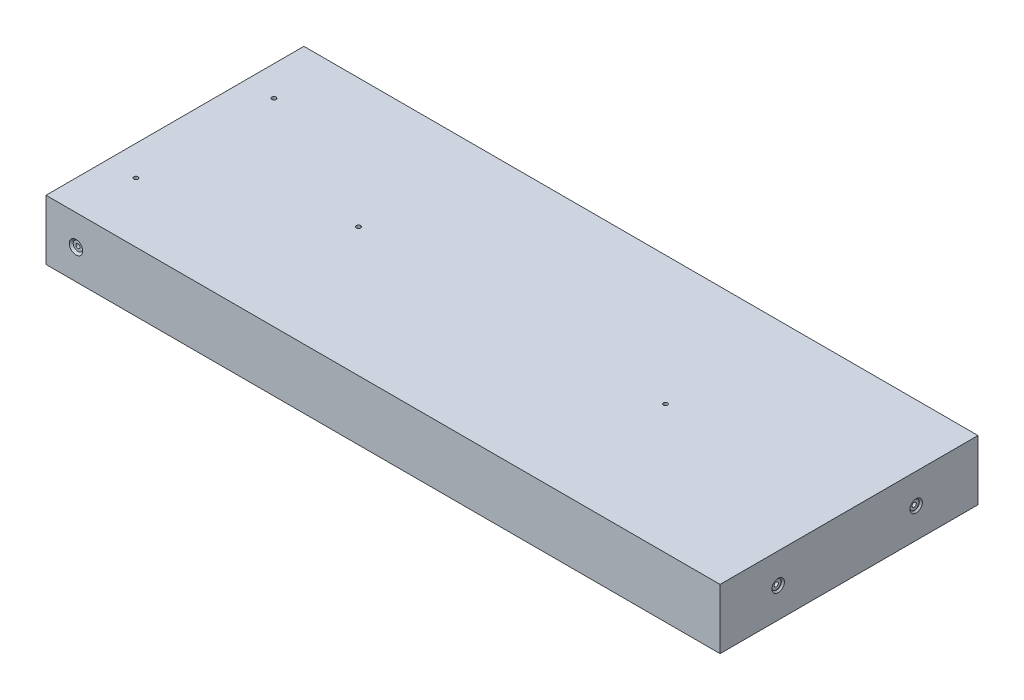
SolidWorks part; units mm, degrees
ref_plane "Front Plane" through (0, 0, 0) normal (0, 0, 1) x (1, 0, 0)
ref_plane "Top Plane" through (0, 0, 0) normal (0, 1, 0) x (1, 0, 0)
ref_plane "Right Plane" through (0, 0, 0) normal (1, 0, 0) x (0, 0, -1)
sketch "Sketch1" plane through (0, 0, 0) normal (0, 1, 0) x (1, 0, 0)
  line L1 (-142.7, 54.6) -> (142.7, 54.6)
  line L2 (-142.7, 54.6) -> (-142.7, -54.6)
  line L3 (-142.7, -54.6) -> (142.7, -54.6)
  line L4 (142.7, 54.6) -> (142.7, -54.6)
  line L5 (-142.7, 54.6) -> (142.7, -54.6) construction
  line L6 (-142.7, -54.6) -> (142.7, 54.6) construction
  point P0 (0, 0)
  dimension "D1" = 109.2
  dimension "D2" = 285.4
extrude "Boss-Extrude1" add sketch "Sketch1" along normal blind 25.4
hole_wizard "CBORE for #0 Binding Head Machine Screw1" positions "Sketch2" profile "Sketch3" counterbore size "#0" standard "ANSI Inch"
sketch "Sketch2" plane through (0, 0, 54.6) normal (0, 0, 1) x (1, 0, 0)
  line L0 (-142.7, 25.4) -> (-142.7, 0) construction
  line L1 (-142.7, 25.4) -> (142.7, 25.4) construction
  point P0 (-130, 12.7)
  dimension "D1" = 12.7
  dimension "D2" = 12.7
sketch "Sketch3" plane through (-130, 12.7, 54.6) normal (1, 0, 0) x (0, -1, 0)
  line L0 (0, 0) -> (0, 30.5342)
  line L1 (0, 30.5342) -> (0.889, 30)
  line L2 (0.889, 30) -> (0.889, 0.8128)
  line L3 (0.889, 0.8128) -> (1.985, 0.8128)
  line L5 (1.985, 0.8128) -> (1.985, 0.8725)
  line L6 (1.985, 0.8725) -> (2.8575, 0)
  line L7 (2.8575, 0) -> (0, 0)
  line L8 (-1.985, 0.8725) -> (-2.8575, 0) construction
  line L10 (0, 30.5342) -> (-0.889, 30) construction
  line L11 (0, -6.35) -> (0, 107.95) construction
  dimension "Hole Dia." = 1.778
  dimension "Hole Depth" = 30
  dimension "C'Bore Dia." = 3.97
  dimension "C'Bore Depth" = 0.8128
  dimension "Near C'Sink Dia." = 5.715
  dimension "Near C'Sink Angle" = 90
  dimension "Drill Angle" = 118
mirror "Mirror1" about plane through (0, 0, 0) normal (0, 0, 1) of "CBORE for #0 Binding Head Machine Screw1"
hole_wizard "CBORE for #0 Binding Head Machine Screw2" positions "Sketch4" profile "Sketch5" counterbore size "#0" standard "ANSI Inch"
sketch "Sketch4" plane through (142.7, 0, 0) normal (1, 0, 0) x (0, 0, -1)
  line L0 (-54.6, 25.4) -> (-54.6, 0) construction
  line L2 (-54.6, 25.4) -> (54.6, 25.4) construction
  point P0 (-30, 12.7)
  point P2 (28.4, 12.7)
  dimension "D1" = 58.4
  dimension "D2" = 24.6
  dimension "D4" = 12.7
sketch "Sketch5" plane through (142.7, 12.7, 30) normal (0, 1, 0) x (0, 0, -1)
  line L0 (0, 0) -> (0, 30.5342)
  line L1 (0, 30.5342) -> (0.889, 30)
  line L2 (0.889, 30) -> (0.889, 0.8128)
  line L3 (0.889, 0.8128) -> (1.985, 0.8128)
  line L5 (1.985, 0.8128) -> (1.985, 0.635)
  line L6 (1.985, 0.635) -> (2.62, 0)
  line L7 (2.62, 0) -> (0, 0)
  line L8 (-1.985, 0.635) -> (-2.62, 0) construction
  line L10 (0, 30.5342) -> (-0.889, 30) construction
  line L11 (0, -6.35) -> (0, 107.95) construction
  dimension "Hole Dia." = 1.778
  dimension "Hole Depth" = 30
  dimension "C'Bore Dia." = 3.97
  dimension "C'Bore Depth" = 0.8128
  dimension "Near C'Sink Dia." = 5.24
  dimension "Near C'Sink Angle" = 90
  dimension "Drill Angle" = 118
hole_wizard "CBORE for #0 Binding Head Machine Screw4" positions "Sketch8" profile "Sketch9" counterbore size "#0" standard "ANSI Inch"
sketch "Sketch8" plane through (0, 0, 0) normal (0, -1, 0) x (-1, 0, 0)
  line L0 (0, 54.6) -> (0, -54.6) construction
  line L1 (-142.7, 54.6) -> (142.7, 54.6) construction
  line L2 (142.7, -54.6) -> (-142.7, -54.6) construction
  line L4 (142.7, 0) -> (-142.7, 0) construction
  line L5 (142.7, 54.6) -> (142.7, -54.6) construction
  line L6 (-142.7, -54.6) -> (-142.7, 54.6) construction
  point P0 (65, 0)
  point P2 (-65, 0)
  dimension "D1" = 130
sketch "Sketch9" plane through (-65, 0, 0) normal (1, 0, 0) x (0, 0, -1)
  line L0 (0, 0) -> (0, 30.5342)
  line L1 (0, 30.5342) -> (0.889, 30)
  line L2 (0.889, 30) -> (0.889, 0.8128)
  line L3 (0.889, 0.8128) -> (1.985, 0.8128)
  line L5 (1.985, 0.8128) -> (1.985, 0.8725)
  line L6 (1.985, 0.8725) -> (2.8575, 0)
  line L7 (2.8575, 0) -> (0, 0)
  line L8 (-1.985, 0.8725) -> (-2.8575, 0) construction
  line L10 (0, 30.5342) -> (-0.889, 30) construction
  line L11 (0, -6.35) -> (0, 107.95) construction
  dimension "Hole Dia." = 1.778
  dimension "Hole Depth" = 30
  dimension "C'Bore Dia." = 3.97
  dimension "C'Bore Depth" = 0.8128
  dimension "Near C'Sink Dia." = 5.715
  dimension "Near C'Sink Angle" = 90
  dimension "Drill Angle" = 118
hole_wizard "CBORE for #0 Binding Head Machine Screw6" positions "Sketch12" profile "Sketch13" counterbore size "#0" standard "ANSI Inch" end condition through all
sketch "Sketch12" plane through (0, 0, 0) normal (0, -1, 0) x (-1, 0, 0)
  line L0 (142.7, 54.6) -> (142.7, -54.6) construction
  line L1 (-142.7, 54.6) -> (142.7, 54.6) construction
  point P0 (130, 29.2)
  point P2 (130, -29.2)
  point P12 (130, 16.1665)
  dimension "D1" = 12.7
  dimension "D2" = 12.7
  dimension "D3" = 58.4
  dimension "D4" = 25.4
sketch "Sketch13" plane through (-130, 0, -29.2) normal (1, 0, 0) x (0, 0, -1)
  line L0 (0, 0) -> (0, 25.4)
  line L1 (0, 25.4) -> (0.889, 25.4)
  line L3 (0.889, 25.4) -> (0.889, 0.8128)
  line L4 (1.985, 0.8128) -> (0.889, 0.8128)
  line L5 (1.985, 0.8128) -> (1.985, 0.8725)
  line L6 (1.985, 0.8725) -> (2.8575, 0)
  line L7 (2.8575, 0) -> (0, 0)
  line L8 (-1.985, 0.8725) -> (-2.8575, 0) construction
  line L11 (0, -6.35) -> (0, 107.95) construction
  dimension "Thru Hole Dia." = 1.778
  dimension "Thru Hole Depth" = 25.4
  dimension "C'Bore Dia." = 3.97
  dimension "C'Bore Depth" = 0.8128
  dimension "Near C'Sink Dia." = 5.715
  dimension "Near C'Sink Angle" = 90
